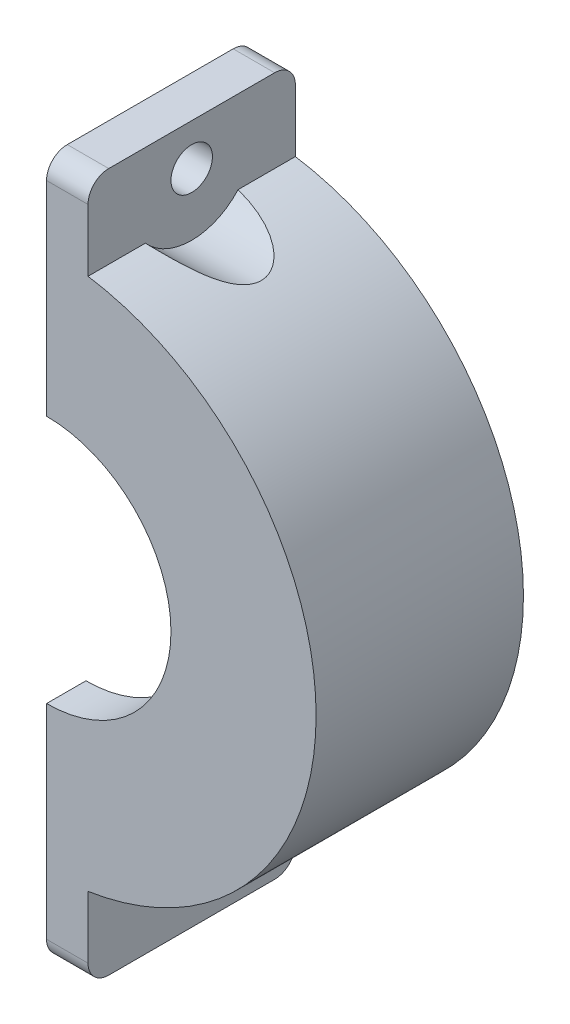
SolidWorks part; units mm, degrees
material "Polylactide (PLA)"
ref_plane "Front Plane" through (0, 0, 0) normal (0, 0, 1) x (1, 0, 0)
ref_plane "Top Plane" through (0, 0, 0) normal (0, 1, 0) x (1, 0, 0)
ref_plane "Right Plane" through (0, 0, 0) normal (1, 0, 0) x (0, 0, -1)
sketch "Sketch1" plane through (0, 0, 0) normal (0, 0, 1) x (1, 0, 0)
  circle A1 centre (0, 0) radius 13
  dimension "D1" = 26
extrude "Boss-Extrude1" add sketch "Sketch1" along normal blind 10
sketch "Sketch2" plane through (0, 0, 10) normal (0, 0, 1) x (1, 0, 0)
  line L0 (0, 0) -> (0, -13.8495)
  line L1 (0, -13.8495) -> (-21.4432, -13.8495)
  line L2 (-21.4432, -13.8495) -> (-21.4432, 14.1852)
  line L3 (-21.4432, 14.1852) -> (0, 14.1852)
  line L4 (0, 14.1852) -> (0, 0)
extrude "Cut-Extrude1" cut sketch "Sketch2" against normal blind 10
sketch "Sketch4" plane through (0, 0, 0) normal (0, 0, -1) x (-1, 0, 0)
  circle A0 centre (0, 0) radius 11
  dimension "D1" = 22
extrude "Cut-Extrude2" cut sketch "Sketch4" against normal blind 8.1
sketch "Sketch5" plane through (0, 0, 0) normal (0, 1, 0) x (1, 0, 0)
  line L0 (0, -10) -> (13, -10) construction
  line L1 (0, 0) -> (2, 0)
  line L2 (0, 0) -> (0, -10)
  line L3 (0, -10) -> (2, -10)
  line L4 (2, 0) -> (2, -10)
  dimension "D1" = 2
extrude "Boss-Extrude2" add sketch "Sketch5" along normal blind 5 from offset 11.8452
extrude "Boss-Extrude3" add sketch "Sketch5<2>" along normal blind 5 from offset 16.8452 offset against normal yes
sketch "Sketch5<2>" plane through (0, 0, 0) normal (0, 1, 0) x (1, 0, 0) same geometry as "Sketch5"
sketch "Sketch6" plane through (2, 0, 0) normal (1, 0, 0) x (0, 0, -1)
  line L0 (-10, 16.8452) -> (-10, 12.8452) construction
  line L1 (-10, 16.8452) -> (0, 16.8452) construction
  circle A0 centre (-5, 14.8452) radius 1
  dimension "D1" = 5
  dimension "D2" = 2
  dimension "D3" = 2
extrude "Cut-Extrude3" cut sketch "Sketch6" against normal blind 5
sketch "Sketch7" plane through (2, 0, 0) normal (1, 0, 0) x (0, 0, -1)
  line L0 (-10, -12.8452) -> (-10, -16.8452) construction
  line L1 (-10, -16.8452) -> (0, -16.8452) construction
  circle A0 centre (-5, -14.8452) radius 1
  dimension "D1" = 5
  dimension "D2" = 2
  dimension "D3" = 2
extrude "Cut-Extrude4" cut sketch "Sketch7" against normal blind 5
sketch "Sketch8" plane through (0, 0, 8.1) normal (0, 0, -1) x (-1, 0, 0)
  line L0 (0, -11) -> (0, 11) construction
  circle A0 centre (0, 0) radius 6
  dimension "D1" = 12
extrude "Cut-Extrude5" cut sketch "Sketch8" against normal blind 10
sketch "Sketch9" plane through (0, 0, 0) normal (1, 0, 0) x (0, 0, -1)
  circle A0 centre (-5, 14.8452) radius 3
  dimension "D1" = 6
extrude "Cut-Extrude6" cut sketch "Sketch9" against normal blind 8 from offset 10
sketch "Sketch10" plane through (0, 0, 0) normal (1, 0, 0) x (0, 0, -1)
  circle A1 centre (-5, -14.8452) radius 3
  dimension "D1" = 6
extrude "Cut-Extrude7" cut sketch "Sketch10" against normal blind 8 from offset 10
fillet "Fillet1" radius 1 1 edges at (1, -16.8452, 0)
fillet "Fillet2" radius 1 1 edges at (1, 16.8452, 0)
fillet "Fillet3" radius 1 1 edges at (1, 16.8452, 10)
fillet "Fillet4" radius 1 1 edges at (1, -16.8452, 10)
